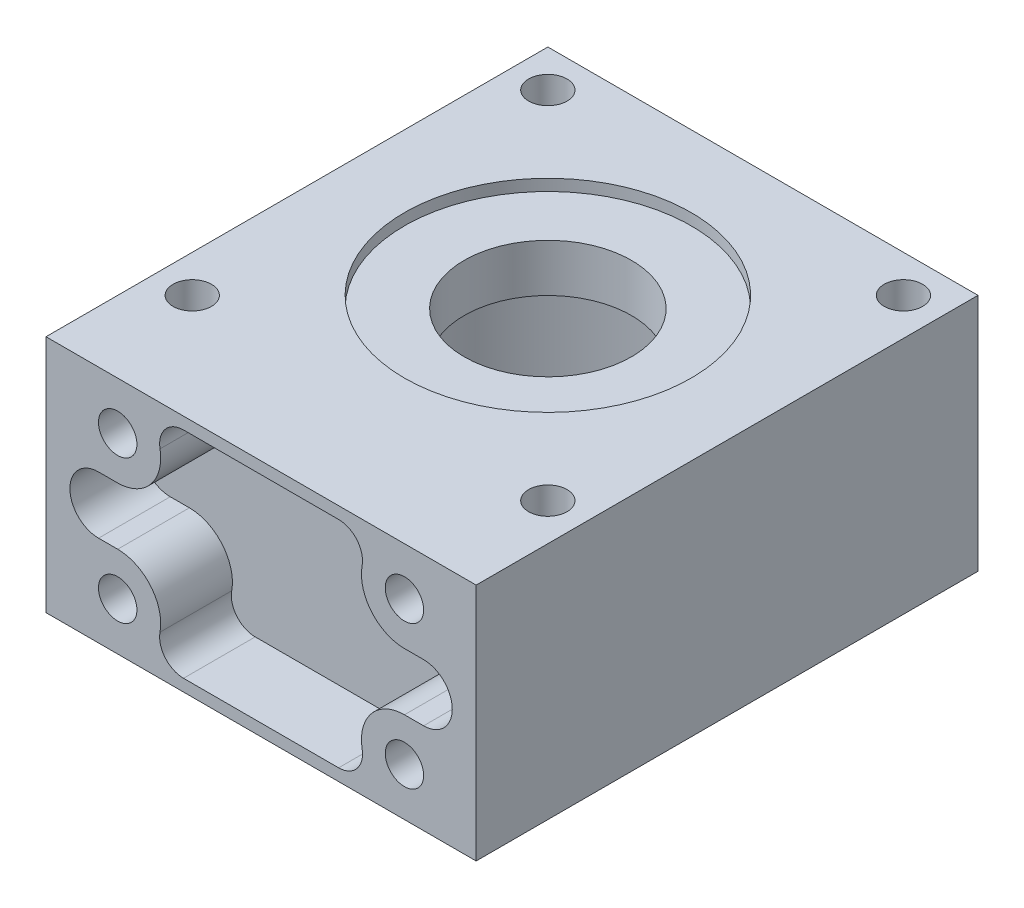
SolidWorks part; units mm, degrees
material "6061 Alloy"
ref_plane "Front" through (0, 0, 0) normal (0, 0, 1) x (1, 0, 0)
ref_plane "Top" through (0, 0, 0) normal (0, 1, 0) x (1, 0, 0)
ref_plane "Right" through (0, 0, 0) normal (1, 0, 0) x (0, 0, -1)
sketch "Sketch1" plane through (0, 0, 0) normal (0, 1, 0) x (1, 0, 0)
  line L0 (28.575, 28.575) -> (-28.575, 28.575)
  line L1 (-28.575, 28.575) -> (28.575, 28.575) construction
  line L2 (-28.575, 28.575) -> (-28.575, -28.575)
  line L3 (-28.575, -28.575) -> (28.575, -28.575) construction
  line L4 (28.575, 28.575) -> (28.575, -28.575)
  line L5 (-28.575, 28.575) -> (28.575, -28.575) construction
  line L6 (-28.575, -28.575) -> (28.575, 28.575) construction
  line L7 (-23.622, 23.622) -> (23.622, 23.622) construction
  line L8 (-23.622, 23.622) -> (-23.622, -23.622) construction
  line L9 (-23.622, -23.622) -> (23.622, -23.622) construction
  line L10 (23.622, 23.622) -> (23.622, -23.622) construction
  line L11 (-23.622, 23.622) -> (23.622, -23.622) construction
  line L12 (-23.622, -23.622) -> (23.622, 23.622) construction
  line L15 (-28.575, -28.575) -> (-28.575, -38.1)
  line L16 (-28.575, -38.1) -> (28.575, -38.1)
  line L17 (28.575, -38.1) -> (28.575, -28.575)
  circle A0 centre (23.622, -23.622) radius 2.5527
  circle A1 centre (23.622, 23.622) radius 2.5527
  circle A2 centre (-23.622, 23.622) radius 2.5527
  circle A3 centre (-23.622, -23.622) radius 2.5527
  point P0 (0, 0)
  point P6 (0, 0)
  dimension "D3" = 5.1054
  dimension "D1" = 57.15
  dimension "D2" = 47.244
  dimension "D4" = 9.525
extrude "Boss-Extrude1" add sketch "Sketch1" along normal blind 31.75
sketch "Sketch2" plane through (0, 31.75, 0) normal (0, 1, 0) x (1, 0, 0)
  circle A0 centre (0, 0) radius 19.05
  dimension "D1" = 38.1
extrude "Cut-Extrude1" cut sketch "Sketch2" against normal blind 1.524
sketch "Sketch3" plane through (0, 30.226, 0) normal (0, 1, 0) x (1, 0, 0)
  circle A0 centre (0, 0) radius 11.1125
  dimension "D1" = 22.225
extrude "Cut-Extrude2" cut sketch "Sketch3" against normal through all
sketch "Sketch4" plane through (0, 0, 0) normal (0, -1, 0) x (1, 0, 0)
  line L0 (0, 0) -> (0, 28.575) construction
  line L2 (0, 0) -> (13.0457, 20.2994) construction
  line L5 (-28.575, 28.575) -> (28.575, 28.575) construction
  circle A0 centre (0, 0) radius 21.844 construction
  circle A1 centre (0, 0) radius 24.13 construction
  arc A2 (0, 20.955) -> (2.8224, 22.6758) centre (0, 24.13) ccw
  arc A3 (11.3291, 17.6285) -> (9.8851, 20.602) centre (13.0457, 20.2994) cw
  arc A4 (2.8224, 22.6758) -> (9.8851, 20.602) centre (6.1542, 20.9592) cw
  arc A5 (11.3291, 17.6285) -> (14.6338, 17.5502) centre (13.0457, 20.2994) ccw
  arc A6 (14.6338, 17.5502) -> (19.4542, 11.9872) centre (16.5086, 14.3048) cw
  arc A7 (19.0613, 8.705) -> (19.4542, 11.9872) centre (21.9494, 10.024) cw
  arc A8 (19.0613, 8.705) -> (21.7991, 6.8525) centre (21.9494, 10.024) ccw
  arc A9 (21.7991, 6.8525) -> (22.8467, -0.4334) centre (21.6217, 3.1087) cw
  arc A10 (20.7417, -2.9822) -> (22.8467, -0.4334) centre (23.8844, -3.4341) cw
  arc A11 (20.7417, -2.9822) -> (22.0433, -6.0208) centre (23.8844, -3.4341) ccw
  arc A12 (22.0433, -6.0208) -> (18.9855, -12.7165) centre (19.87, -9.0743) cw
  arc A13 (15.8367, -13.7226) -> (18.9855, -12.7165) centre (18.2362, -15.8018) cw
  arc A14 (15.8367, -13.7226) -> (15.289, -16.9825) centre (18.2362, -15.8018) ccw
  arc A15 (15.289, -16.9825) -> (9.0966, -20.9621) centre (11.8098, -18.3763) cw
  arc A16 (5.9037, -20.1062) -> (9.0966, -20.9621) centre (6.7982, -23.1526) cw
  arc A17 (5.9037, -20.1062) -> (3.6804, -22.5524) centre (6.7982, -23.1526) ccw
  arc A18 (3.6804, -22.5524) -> (-3.6804, -22.5524) centre (0, -21.844) cw
  arc A19 (-5.9037, -20.1062) -> (-3.6804, -22.5524) centre (-6.7982, -23.1526) cw
  arc A20 (-5.9037, -20.1062) -> (-9.0966, -20.9621) centre (-6.7982, -23.1526) ccw
  arc A21 (-9.0966, -20.9621) -> (-15.289, -16.9825) centre (-11.8098, -18.3763) cw
  arc A22 (-15.8367, -13.7226) -> (-15.289, -16.9825) centre (-18.2362, -15.8018) cw
  arc A23 (-15.8367, -13.7226) -> (-18.9855, -12.7165) centre (-18.2362, -15.8018) ccw
  arc A24 (-18.9855, -12.7165) -> (-22.0433, -6.0208) centre (-19.87, -9.0743) cw
  arc A25 (-20.7417, -2.9822) -> (-22.0433, -6.0208) centre (-23.8844, -3.4341) cw
  arc A26 (-20.7417, -2.9822) -> (-22.8467, -0.4334) centre (-23.8844, -3.4341) ccw
  arc A27 (-22.8467, -0.4334) -> (-21.7991, 6.8525) centre (-21.6217, 3.1087) cw
  arc A28 (-19.0613, 8.705) -> (-21.7991, 6.8525) centre (-21.9494, 10.024) cw
  arc A29 (-19.0613, 8.705) -> (-19.4542, 11.9872) centre (-21.9494, 10.024) ccw
  arc A30 (-19.4542, 11.9872) -> (-14.6338, 17.5502) centre (-16.5086, 14.3048) cw
  arc A31 (-11.3291, 17.6285) -> (-14.6338, 17.5502) centre (-13.0457, 20.2994) cw
  arc A32 (-11.3291, 17.6285) -> (-9.8851, 20.602) centre (-13.0457, 20.2994) ccw
  arc A33 (-9.8851, 20.602) -> (-2.8224, 22.6758) centre (-6.1542, 20.9592) cw
  arc A34 (0, 20.955) -> (-2.8224, 22.6758) centre (0, 24.13) cw
  point P14 (0, 28.575)
  point P87 (0, 0)
  dimension "D1" = 48.26
  dimension "D2" = 43.688
  dimension "D4" = 3.175
  dimension "D5" = 3.175
  dimension "D3" = 32.727
  dimension "D6" = 11
extrude "Cut-Extrude3" cut sketch "Sketch4" against normal blind 23.876
sketch "Sketch5" plane through (0, 0, 0) normal (0, -1, 0) x (1, 0, 0)
  circle A0 centre (0, 0) radius 26.1937
  dimension "D1" = 52.3875
extrude "Cut-Extrude4" cut sketch "Sketch5" against normal blind 17.526
sketch "Sketch7" plane through (0, 0, 0) normal (0, -1, 0) x (1, 0, 0)
  line L0 (-28.575, -28.575) -> (28.575, -28.575) construction
  line L4 (-28.575, -28.575) -> (-28.575, 38.1) construction
  line L5 (-23.8125, 26.9875) -> (23.8125, 26.9875)
  line L6 (-26.9875, 23.8125) -> (-26.9875, -23.8125)
  line L7 (-23.8125, -26.9875) -> (23.8125, -26.9875)
  line L8 (26.9875, 23.8125) -> (26.9875, -23.8125)
  line L9 (-26.9875, 26.9875) -> (26.9875, -26.9875) construction
  line L10 (-26.9875, -26.9875) -> (26.9875, 26.9875) construction
  arc A0 (-26.9875, -23.8125) -> (-23.8125, -26.9875) centre (-23.8125, -23.8125) ccw
  arc A2 (23.8125, -26.9875) -> (26.9875, -23.8125) centre (23.8125, -23.8125) ccw
  arc A3 (23.8125, 26.9875) -> (26.9875, 23.8125) centre (23.8125, 23.8125) cw
  arc A4 (-23.8125, 26.9875) -> (-26.9875, 23.8125) centre (-23.8125, 23.8125) ccw
  point P0 (0, 0)
  dimension "D1" = 1.5875
  dimension "D3" = 3.175
  dimension "D2" = 1.5875
extrude "Cut-Extrude5" cut sketch "Sketch7" against normal blind 1.5875
ref_plane "Plane1" through (0, 0, 28.575) normal (0, 0, 1) x (1, 0, 0)
sketch "Sketch10" plane through (0, 0, 38.1) normal (0, 0, 1) x (1, 0, 0)
  line L0 (28.575, 31.75) -> (28.575, 0) construction
  line L1 (19.05, 25.4) -> (-19.05, 25.4)
  line L2 (19.05, 25.4) -> (19.05, 6.35)
  line L3 (19.05, 6.35) -> (-19.05, 6.35)
  line L4 (-19.05, 25.4) -> (-19.05, 6.35)
  line L5 (19.05, 25.4) -> (-19.05, 6.35) construction
  line L6 (19.05, 6.35) -> (-19.05, 25.4) construction
  line L7 (-28.575, 0) -> (28.575, 0) construction
  point P0 (0, 15.875)
  point P7 (28.575, 15.875)
  point P10 (0, 0)
  dimension "D1" = 38.1
  dimension "D2" = 19.05
hole_wizard "1/4-20 Tapped Hole1" positions "Sketch12" profile "Sketch11" tap size "1/4-20" standard "ANSI Inch"
sketch "Sketch12" plane through (0, 0, 38.1) normal (0, 0, 1) x (1, 0, 0)
  point P0 (-19.05, 25.4)
  point P3 (19.05, 25.4)
  point P6 (19.05, 6.35)
  point P9 (-19.05, 6.35)
sketch "Sketch11" plane through (-19.05, 25.4, 38.1) normal (1, 0, 0) x (0, -1, 0)
  line L0 (0, 0) -> (0, 11.1858)
  line L1 (0, 11.1858) -> (2.5527, 9.652)
  line L2 (2.5527, 9.652) -> (2.5527, 0)
  line L5 (2.5527, 0) -> (0, 0)
  line L10 (0, 11.1858) -> (-2.5527, 9.652) construction
  line L11 (0, -6.35) -> (0, 107.95) construction
  dimension "Tap Drill Dia." = 5.1054
  dimension "Tap Drill Depth" = 9.652
  dimension "Drill Angle" = 118
sketch "Sketch13" plane through (0, 0, 38.1) normal (0, 0, 1) x (1, 0, 0)
  line L0 (-28.575, 15.875) -> (0, 15.875) construction
  line L1 (-28.575, 31.75) -> (-28.575, 0) construction
  line L2 (0, 15.875) -> (0, 0) construction
  line L3 (-21.59, 12.065) -> (-19.05, 12.065)
  line L4 (-10.3029, 30.1625) -> (10.3029, 30.1625)
  line L5 (-10.3029, 1.5875) -> (10.3029, 1.5875)
  line L6 (-28.575, 0) -> (28.575, 0) construction
  line L7 (-21.59, 19.685) -> (-19.05, 19.685)
  line L8 (21.59, 12.065) -> (19.05, 12.065)
  line L9 (21.59, 19.685) -> (19.05, 19.685)
  arc A0 (-21.59, 19.685) -> (-21.59, 12.065) centre (-21.59, 15.875) ccw
  arc A1 (-19.05, 12.065) -> (-13.4269, 5.3295) centre (-19.05, 6.35) cw
  arc A2 (-13.4269, 5.3295) -> (-10.3029, 1.5875) centre (-10.3029, 4.7625) ccw
  arc A3 (-13.4269, 26.4205) -> (-10.3029, 30.1625) centre (-10.3029, 26.9875) cw
  arc A4 (-19.05, 19.685) -> (-13.4269, 26.4205) centre (-19.05, 25.4) ccw
  arc A5 (13.4269, 5.3295) -> (10.3029, 1.5875) centre (10.3029, 4.7625) cw
  arc A6 (19.05, 12.065) -> (13.4269, 5.3295) centre (19.05, 6.35) ccw
  arc A7 (21.59, 19.685) -> (21.59, 12.065) centre (21.59, 15.875) cw
  arc A8 (19.05, 19.685) -> (13.4269, 26.4205) centre (19.05, 25.4) cw
  arc A9 (13.4269, 26.4205) -> (10.3029, 30.1625) centre (10.3029, 26.9875) ccw
  point P14 (-25.4, 15.875)
  point P23 (0, 1.5875)
  point P35 (0, 30.1625)
  dimension "D1" = 1.5875
  dimension "D2" = 3.175
  dimension "D3" = 5.715
  dimension "D4" = 3.175
extrude "Cut-Extrude6" cut sketch "Sketch13" against normal offset from surface (9.525 mm away) 1.5875 up to face at (0, 0.7937, 26.9875)
sketch "Sketch14" plane through (0, 0, 28.575) normal (0, 0, 1) x (1, 0, 0)
  line L1 (9.525, 3.1825) -> (-9.525, 3.1825)
  line L2 (12.7, 6.3575) -> (12.7, 25.4075)
  line L3 (9.525, 28.5825) -> (-9.525, 28.5825)
  line L4 (-12.7, 6.3575) -> (-12.7, 25.4075)
  line L5 (12.7, 3.1825) -> (-12.7, 28.5825) construction
  line L6 (12.7, 28.5825) -> (-12.7, 3.1825) construction
  arc A0 (9.525, 3.1825) -> (12.7, 6.3575) centre (9.525, 6.3575) ccw
  arc A1 (-9.525, 3.1825) -> (-12.7, 6.3575) centre (-9.525, 6.3575) cw
  arc A2 (12.7, 25.4075) -> (9.525, 28.5825) centre (9.525, 25.4075) ccw
  arc A3 (-12.7, 25.4075) -> (-9.525, 28.5825) centre (-9.525, 25.4075) cw
  point P0 (0, 15.8825)
  dimension "D2" = 3.175
  dimension "D1" = 25.4
  dimension "D3" = 25.4
